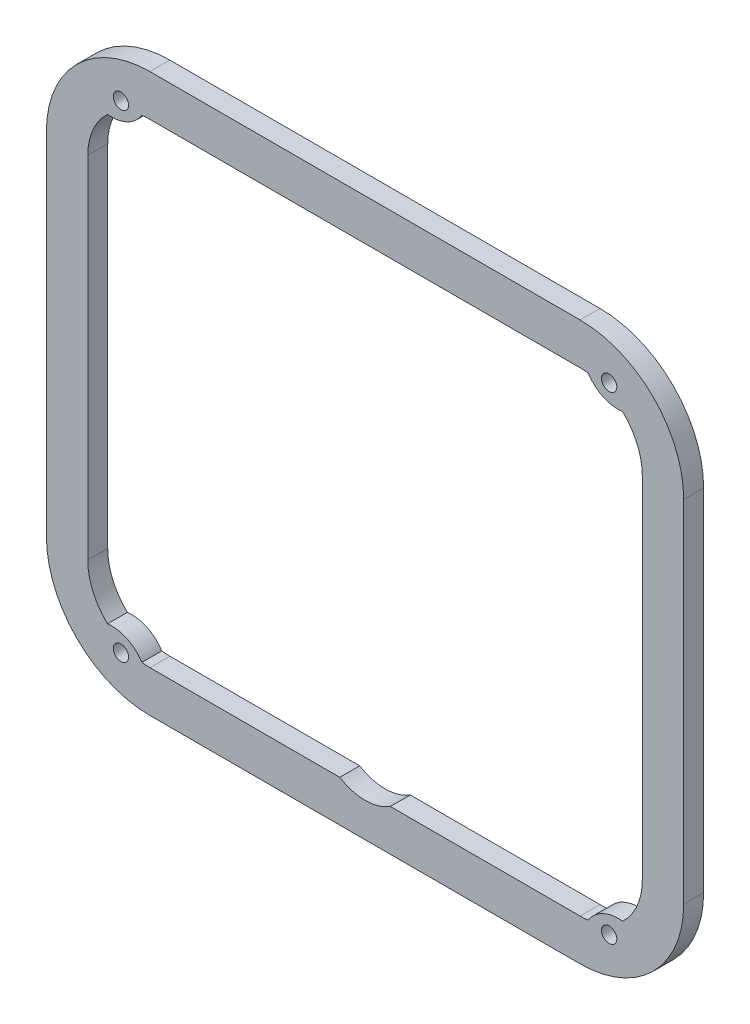
SolidWorks part; units mm, degrees
material "Delrin"
ref_plane "Front Plane" through (0, 0, 0) normal (0, 0, 1) x (1, 0, 0)
ref_plane "Top Plane" through (0, 0, 0) normal (0, 1, 0) x (1, 0, 0)
ref_plane "Right Plane" through (0, 0, 0) normal (1, 0, 0) x (0, 0, -1)
sketch "Sketch1" plane through (0, 0, 0) normal (0, 0, 1) x (1, 0, 0)
  line L0 (-17.145, -18.923) -> (-2.0127, -18.923)
  line L1 (17.145, 22.225) -> (-17.145, 22.225)
  line L2 (25.4, 13.97) -> (25.4, -13.97)
  line L3 (17.145, -22.225) -> (-17.145, -22.225)
  line L4 (-25.4, 13.97) -> (-25.4, -13.97)
  line L5 (25.4, 22.225) -> (-25.4, -22.225) construction
  line L6 (25.4, -22.225) -> (-25.4, 22.225) construction
  line L7 (2.0127, -18.923) -> (17.145, -18.923)
  line L10 (-22.098, 13.97) -> (-22.098, -13.97)
  line L13 (22.098, 13.97) -> (22.098, -13.97)
  line L14 (17.145, 18.923) -> (-17.145, 18.923)
  line L18 (0, 18.415) -> (0, -18.415) construction
  line L19 (-1007.9925, 0) -> (48992.0075, 0) construction
  line L36 (17.145, -18.923) -> (-17.145, -18.923) construction
  arc A0 (-2.0127, -18.923) -> (2.0127, -18.923) centre (0, -15.748) ccw
  arc A1 (-17.145, 22.225) -> (-25.4, 13.97) centre (-17.145, 13.97) ccw
  arc A2 (17.145, 22.225) -> (25.4, 13.97) centre (17.145, 13.97) cw
  arc A3 (25.4, -13.97) -> (17.145, -22.225) centre (17.145, -13.97) cw
  arc A4 (-17.145, -22.225) -> (-25.4, -13.97) centre (-17.145, -13.97) cw
  arc A5 (-22.098, -13.97) -> (-17.145, -18.923) centre (-17.145, -13.97) ccw
  arc A6 (17.145, -18.923) -> (22.098, -13.97) centre (17.145, -13.97) ccw
  arc A7 (17.145, 18.923) -> (22.098, 13.97) centre (17.145, 13.97) cw
  arc A8 (-17.145, 18.923) -> (-22.098, 13.97) centre (-17.145, 13.97) ccw
  circle A9 centre (-19.4575, 19.05) radius 0.6096
  circle A10 centre (19.4575, 19.05) radius 0.6096
  circle A11 centre (19.4575, -19.05) radius 0.6096
  circle A12 centre (-19.4575, -19.05) radius 0.6096
  arc A13 (-17.145, -18.923) -> (-22.098, -13.97) centre (-17.145, -13.97) cw construction
  arc A14 (22.098, -13.97) -> (17.145, -18.923) centre (17.145, -13.97) cw construction
  arc A15 (-20.5287, 17.5871) -> (-17.7896, 18.8809) centre (-20.1849, 20.4056) ccw
  arc A16 (20.5287, 17.5871) -> (17.7896, 18.8809) centre (20.1849, 20.4056) cw
  arc A17 (20.5287, -17.5871) -> (17.7896, -18.8809) centre (20.1849, -20.4056) ccw
  arc A18 (-20.5287, -17.5871) -> (-17.7896, -18.8809) centre (-20.1849, -20.4056) cw
  point P0 (0, 0)
  dimension "D4" = 7.5184
  dimension "D6" = 8.255
  dimension "D7" = 8.255
  dimension "D8" = 8.255
  dimension "D9" = 8.255
  dimension "D5" = 1.2192
  dimension "D1" = 50.8
  dimension "D2" = 44.45
  dimension "D10" = 3.302
  dimension "D3" = 3.175
  dimension "D11" = 19.05
extrude "Boss-Extrude1" add sketch "Sketch1" along normal blind 1.5875 contours A4 L3 A3 L2 A2 L1 A1 L4 A10 A9 A8 L14 A7 L13 A6 L7 A0 L0 A5 L10 A11 A12 | A8 A15 | A18 A5 | A6 A17 | A16 A7 region at (-19.1243, -18.1602, 0) region at (19.1243, -18.1602, 0) region at (-19.1243, 18.1602, 0) region at (19.1243, 18.1602, 0) region at (22.5049, 19.3299, 0)
